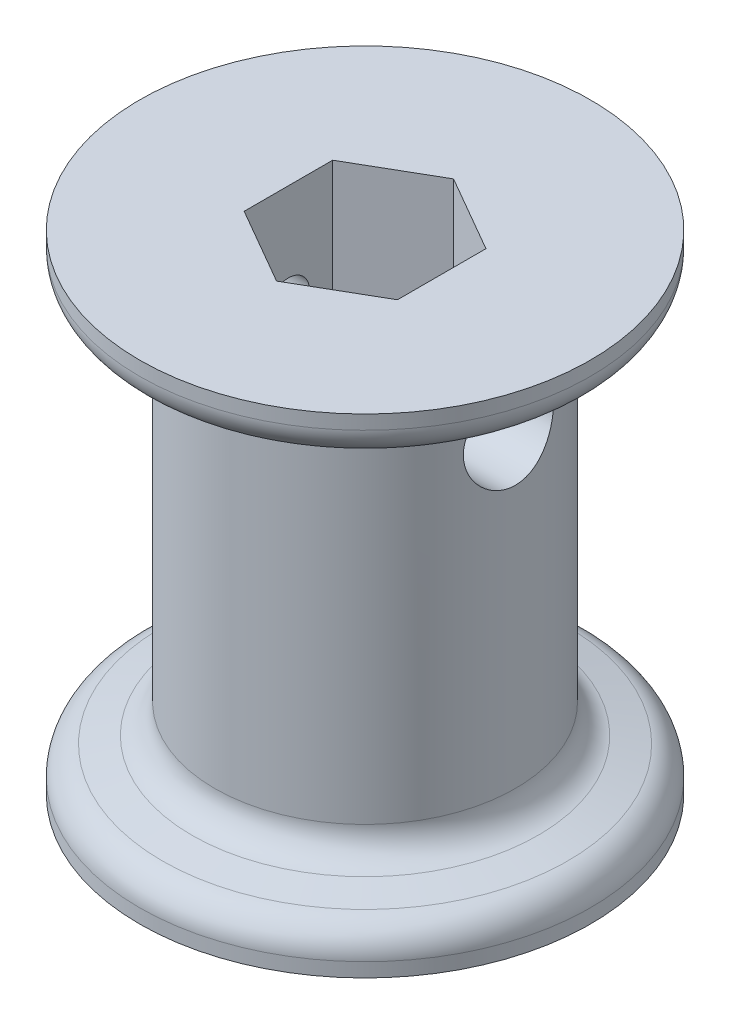
SolidWorks part; units mm, degrees
material "PET"
ref_plane "Front" through (0, 0, 0) normal (0, 0, 1) x (1, 0, 0)
ref_plane "Top" through (0, 0, 0) normal (0, 1, 0) x (1, 0, 0)
ref_plane "Right" through (0, 0, 0) normal (1, 0, 0) x (0, 0, -1)
sketch "Sketch1" plane through (0, 0, 0) normal (0, 0, 1) x (1, 0, 0)
  line L0 (0, 0) -> (-19.05, 0)
  line L1 (-19.05, 0) -> (-19.05, 1.1918)
  line L2 (-17.126, 3.656) -> (-14.624, 4.2815)
  line L3 (-12.7, 6.7457) -> (-12.7, 34.5293)
  line L4 (-14.624, 36.9935) -> (-17.126, 37.619)
  line L5 (-19.05, 40.0832) -> (-19.05, 41.275)
  line L6 (-19.05, 41.275) -> (0, 41.275)
  line L7 (0, 41.275) -> (0, 0)
  line L8 (0, 41.275) -> (0, -30.7578) construction
  arc A0 (-19.05, 1.1918) -> (-17.126, 3.656) centre (-16.51, 1.1918) cw
  arc A1 (-14.624, 4.2815) -> (-12.7, 6.7457) centre (-15.24, 6.7457) ccw
  arc A2 (-12.7, 34.5293) -> (-14.624, 36.9935) centre (-15.24, 34.5293) ccw
  arc A3 (-17.126, 37.619) -> (-19.05, 40.0832) centre (-16.51, 40.0832) cw
  point P3 (-16.9474, 36.5125)
  point P11 (-25.894, 3.175)
  point P12 (-26.2707, 0)
  point P13 (-14.4812, 36.5125)
  point P16 (-19.05, 3.175)
  point P19 (-12.7, 4.7625)
  point P22 (-12.7, 36.5125)
  point P25 (-19.05, 38.1)
  dimension "D6" = 2.54
  dimension "D1" = 31.75
  dimension "D2" = 3.175
  dimension "D3" = 1.5875
  dimension "D4" = 6.35
  dimension "D5" = 12.7
revolve "Revolve1" add sketch "Sketch1" angle 360 about L8
sketch "Sketch2" plane through (0, 0, 0) normal (0, 0, 1) x (1, 0, 0)
  line L0 (-18.0638, 34.5293) -> (0, 34.5293)
  line L1 (0, 34.5293) -> (0, 36.5613)
  line L2 (0, 36.5613) -> (20.0362, 36.5613)
  line L3 (20.0362, 36.5613) -> (20.0362, 32.7513)
  line L4 (20.0362, 32.7513) -> (-18.0638, 32.7513)
  line L5 (-18.0638, 32.7513) -> (-18.0638, 34.5293)
  line L6 (-20.4723, 32.7513) -> (23.1676, 32.7513) construction
  line L7 (12.7, 34.5293) -> (-12.7, 34.5293) construction
  point P7 (21.2178, 31.9345)
  dimension "D1" = 3.556
  dimension "D2" = 7.62
  dimension "D3" = 38.1
  dimension "D4" = 1.778
revolve "Cut-Revolve1" cut sketch "Sketch2" angle 360 about L6
sketch "Sketch3" plane through (0, 41.275, 0) normal (0, 1, 0) x (1, 0, 0)
  line L0 (0, -7.479) -> (0, 0) construction
  line L1 (6.477, -3.7395) -> (6.477, 3.7395)
  line L2 (6.477, 3.7395) -> (0, 7.479)
  line L3 (0, 7.479) -> (-6.477, 3.7395)
  line L4 (-6.477, 3.7395) -> (-6.477, -3.7395)
  line L5 (-6.477, -3.7395) -> (0, -7.479)
  line L6 (0, -7.479) -> (6.477, -3.7395)
  circle A0 centre (0, 0) radius 6.477 construction
  dimension "D1" = 12.954
extrude "Cut-Extrude1" cut sketch "Sketch3" against normal through all
fillet "Fillet1" radius 1.27 1 edges at (-12.694, 31.0165, -0.3894)
